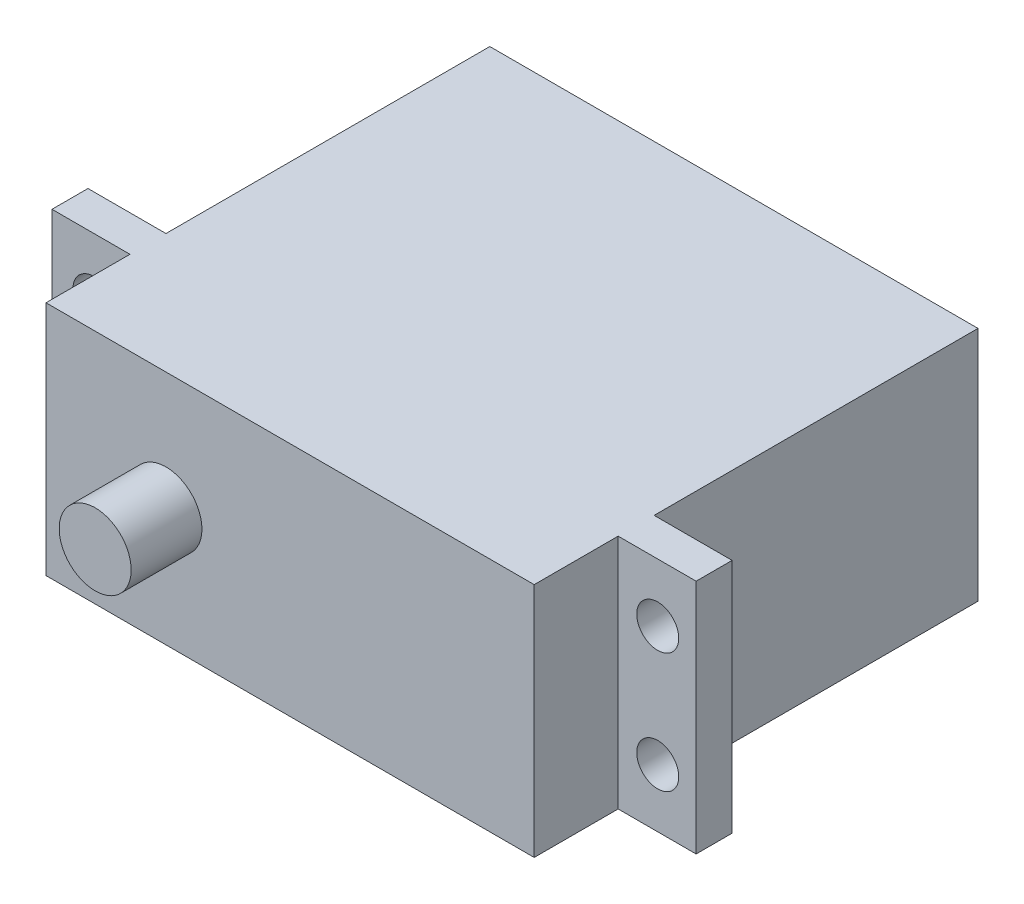
SolidWorks part; units mm, degrees
ref_plane "Front Plane" through (0, 0, 0) normal (0, 0, 1) x (1, 0, 0)
ref_plane "Top Plane" through (0, 0, 0) normal (0, 1, 0) x (1, 0, 0)
ref_plane "Right Plane" through (0, 0, 0) normal (1, 0, 0) x (0, 0, -1)
sketch "Case_40p7x19p7_profile" plane through (0, 0, 0) normal (0, 0, 1) x (1, 0, 0)
  line L1 (-10, -9.85) -> (30.7, -9.85)
  line L2 (-10, -9.85) -> (-10, 9.85)
  line L3 (-10, 9.85) -> (30.7, 9.85)
  line L4 (30.7, -9.85) -> (30.7, 9.85)
extrude "Case_40p7x19p7" add sketch "Case_40p7x19p7_profile" along normal blind 37 from offset 30 offset against normal yes
sketch "Mounting_flange_nominal_profile" plane through (0, 0, 0) normal (0, 0, 1) x (1, 0, 0)
  line L1 (-16.5, -9.85) -> (37.2, -9.85)
  line L2 (-16.5, -9.85) -> (-16.5, 9.85)
  line L3 (-16.5, 9.85) -> (37.2, 9.85)
  line L4 (37.2, -9.85) -> (37.2, 9.85)
extrude "Mounting_flange_nominal" add sketch "Mounting_flange_nominal_profile" along normal blind 3 from offset 3 offset against normal yes
sketch "Output_envelope_not_spline_profile" plane through (0, 0, 0) normal (0, 0, 1) x (1, 0, 0)
  circle A0 centre (0, 0) radius 3
extrude "Output_envelope_not_spline" add sketch "Output_envelope_not_spline_profile" along normal blind 5.9 from offset 7
sketch "Tab_holes_nominal_profile" plane through (0, 0, 0) normal (0, 0, 1) x (1, 0, 0)
  circle A0 centre (-13, 5) radius 1.75
  circle A1 centre (-13, -5) radius 1.75
  circle A2 centre (34, 5) radius 1.75
  circle A3 centre (34, -5) radius 1.75
extrude "Tab_holes_nominal" cut sketch "Tab_holes_nominal_profile" along normal through all from offset 50 offset against normal yes
